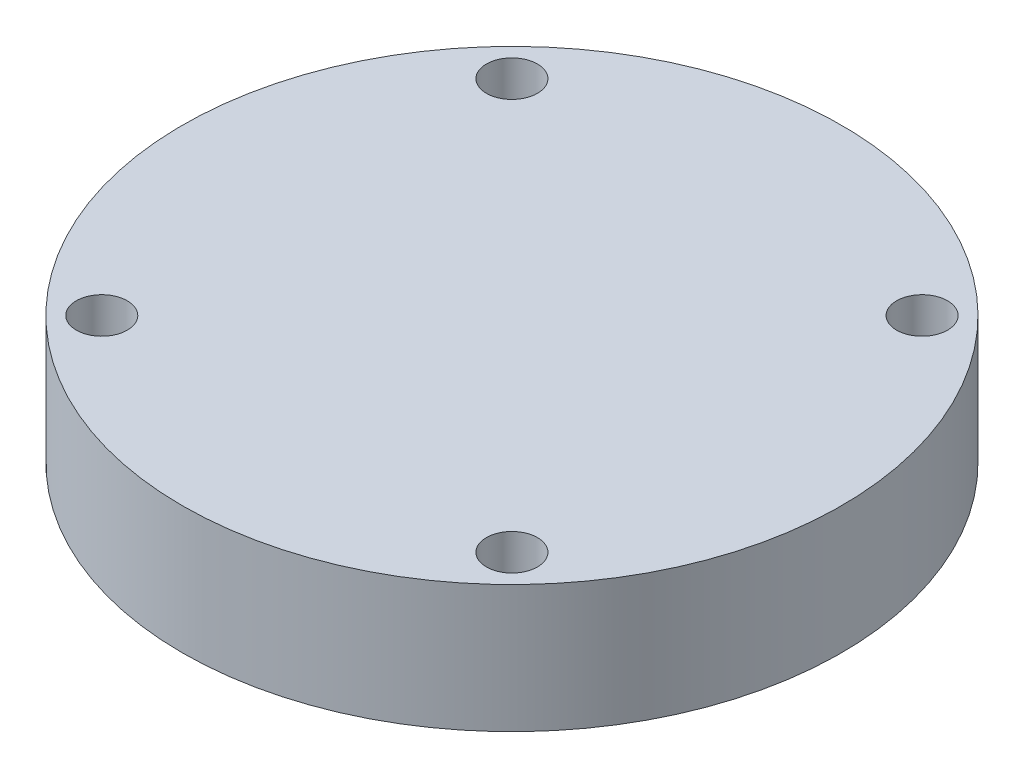
SolidWorks part; units mm, degrees
material "1060 Alloy"
ref_plane "Front Plane" through (0, 0, 0) normal (0, 0, 1) x (1, 0, 0)
ref_plane "Top Plane" through (0, 0, 0) normal (0, 1, 0) x (1, 0, 0)
ref_plane "Right Plane" through (0, 0, 0) normal (1, 0, 0) x (0, 0, -1)
ref_axis "Y Axis" through (0, 6.6675, 0) along (0, -1, 0)
sketch "outer" plane through (0, 0, 0) normal (0, 1, 0) x (1, 0, 0)
  circle A0 centre (0, 0) radius 19.05
  dimension "D1" = 38.1
extrude "Body" add sketch "outer" along normal blind 7.366
sketch "inner" plane through (0, 0, 0) normal (0, 1, 0) x (1, 0, 0)
  circle A0 centre (0, 0) radius 11.938
  dimension "D1" = 23.876
extrude "Pocket" cut sketch "inner" along normal blind 4.826
sketch "Screw Position" plane through (0, 0, 0) normal (0, 1, 0) x (1, 0, 0)
  point P0 (-11.8539, 11.8539)
  dimension "D1" = 16.764
hole_wizard "#4 Clearance Hole1" positions "Sketch7" profile "Sketch8" hole size "#4" standard "ANSI Inch" end condition through all
sketch "Sketch7" plane through (0, 7.366, 0) normal (0, 1, 0) x (1, 0, 0)
  point P0 (-11.8539, 11.8539)
sketch "Sketch8" plane through (-11.8539, 7.366, -11.8539) normal (1, 0, 0) x (0, 0, 1)
  line L0 (0, 0) -> (0, 7.366)
  line L1 (0, 7.366) -> (1.4732, 7.366)
  line L2 (1.4732, 7.366) -> (1.4732, 0)
  line L5 (1.4732, 0) -> (0, 0)
  line L11 (0, -6.35) -> (0, 107.95) construction
  dimension "Thru Hole Dia." = 2.9464
  dimension "Thru Hole Depth" = 7.366
pattern_circular "Screw Holes" count 4 over 360 about axis through (0, 6.6675, 0) along (0, -1, 0) of "#4 Clearance Hole1"
sketch "Post Sketch" plane through (0, 0, 0) normal (0, 1, 0) x (1, 0, 0)
  circle A0 centre (0, -5.715) radius 1
  circle A1 centre (5.2984, -5.2984) radius 1
  point P0 (0, -5.715)
  point P1 (5.2984, -5.2984)
  dimension "D3" = 2
  dimension "D4" = 2
  dimension "D1" = 5.715
extrude "Post" add sketch "Post Sketch" against normal blind 4.826 from surface starting at face at (0, 4.826, 11.938)
pattern_circular "Posts" count 4 over 360 about axis through (0, 6.6675, 0) along (0, -1, 0) of "Post"
sketch "Flat Cut Sketch" plane through (0, 0, 0) normal (0, 1, 0) x (1, 0, 0)
  line L0 (0, 19.05) -> (0, -19.05) construction
  line L1 (-17.78, 19.05) -> (-20.32, -19.05) construction
  line L2 (17.78, -19.05) -> (20.32, -19.05)
  line L3 (17.78, -19.05) -> (17.78, 19.05)
  line L4 (17.78, 19.05) -> (20.32, 19.05)
  line L5 (20.32, -19.05) -> (20.32, 19.05)
  line L6 (17.78, -19.05) -> (20.32, 19.05) construction
  line L7 (17.78, 19.05) -> (20.32, -19.05) construction
  line L8 (-17.78, -19.05) -> (-20.32, 19.05) construction
  line L9 (-20.32, -19.05) -> (-20.32, 19.05)
  line L10 (-17.78, 19.05) -> (-20.32, 19.05)
  line L11 (-17.78, -19.05) -> (-17.78, 19.05)
  line L12 (-17.78, -19.05) -> (-20.32, -19.05)
  circle A0 centre (0, 0) radius 19.05 construction
  point P5 (19.05, 0)
  point P14 (-19.05, 0)
  dimension "D1" = 38.1
  dimension "D2" = 2.54
extrude "Flat Cut" [suppressed] cut sketch "Flat Cut Sketch" along normal through all
equation "\"outer_d\"= 3 / 2in"
equation "\"top_h\"= 1 / 4in"
equation "\"screw_r\"= 0.66in"
equation "\"inner_d\"= 0.94in"
equation "\"inner_h\"= 150mil"
equation "\"D1@outer\" = \"outer_d\""
equation "\"D1@Body\"=\"top_h\" + \"inset_h\""
equation "\"D1@inner\"=\"inner_d\""
equation "\"D1@Pocket\"=\"inner_h\" + \"inset_h\""
equation "\"D1@Screw Position\"=\"screw_r\""
equation "\"post_r1\" = 0.225in"
equation "\"post_r2\"= 0.295in"
equation "\"post_bottom_h\"= 0.04in"
equation "\"D1@Post Sketch\" = \"post_r1\""
equation "\"D2@Post Sketch\" = \"post_r2\""
equation "\"post_d\"= 2mm"
equation "\"D3@Post Sketch\"=\"post_d\""
equation "\"D4@Post Sketch\"=\"post_d\""
equation "\"D1@Post\" = \"inner_h\" + \"post_bottom_h\""
equation "\"inset_h\"= 0.04in"
equation "\"D1@Flat Cut Sketch\" = \"outer_d\""
equation "\"flat_cut\"= 0.05in"
equation "\"D2@Flat Cut Sketch\" = \"flat_cut\" * 2"
